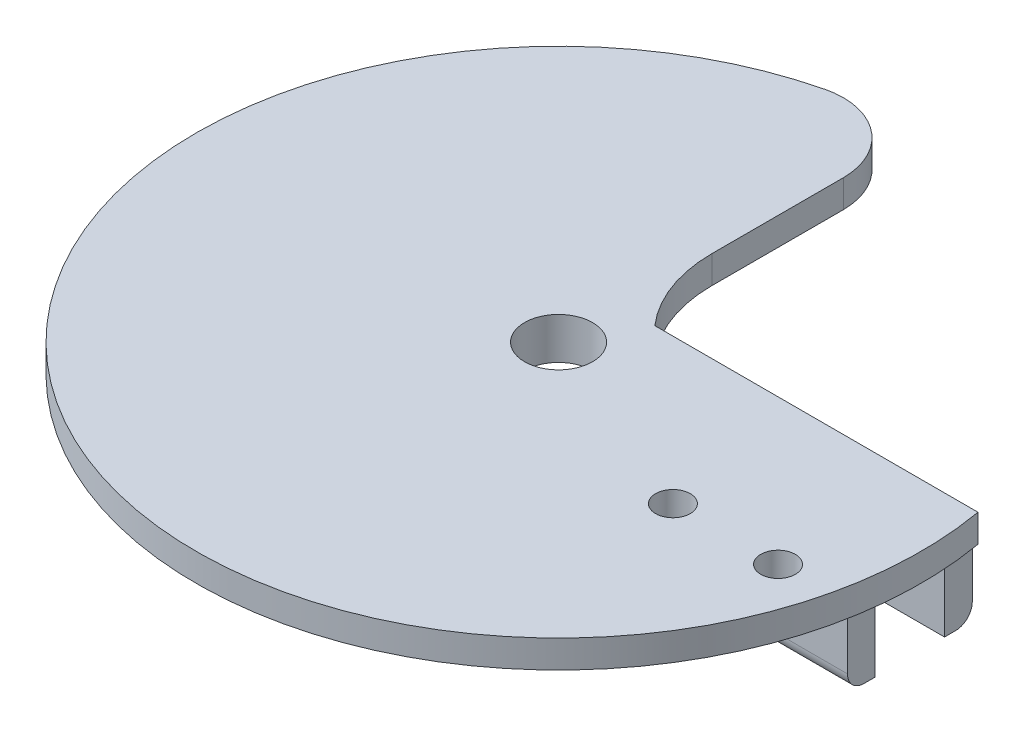
SolidWorks part; units mm, degrees
ref_plane "Front Plane" through (0, 0, 0) normal (0, 0, 1) x (1, 0, 0)
ref_plane "Top Plane" through (0, 0, 0) normal (0, 1, 0) x (1, 0, 0)
ref_plane "Right Plane" through (0, 0, 0) normal (1, 0, 0) x (0, 0, -1)
sketch "Sketch1" plane through (0, 0, 0) normal (0, 1, 0) x (1, 0, 0)
  line L0 (0, 0) -> (26.1327, 0) construction
  line L1 (0, 4.9) -> (0, 26.1327)
  line L2 (11.8897, 4.5) -> (1.9391, 4.5)
  line L3 (11.8897, 4.5) -> (25.3293, 4.5)
  line L4 (11.8897, 4.5) -> (11.8897, 2.5)
  line L5 (11.8897, 2.5) -> (25.3293, 2.5)
  line L6 (25.3293, 4.5) -> (25.3293, 2.5)
  line L7 (11.8897, -2.5) -> (25.3293, -2.5)
  line L8 (11.8897, -2.5) -> (11.8897, -4.5)
  line L9 (11.8897, -4.5) -> (25.3293, -4.5)
  line L10 (25.3293, -2.5) -> (25.3293, -4.5)
  line L11 (25.3293, 4.5) -> (25.7423, 4.5)
  circle A0 centre (0, 0) radius 2.45
  circle A1 centre (0, 0) radius 4.9
  arc A2 (0, 26.1327) -> (25.7423, 4.5) centre (0, 0) ccw
  circle A3 centre (14.2061, -5.9619) radius 1.25
  circle A4 centre (21.7863, -5.9619) radius 1.25
  point P21 (0, 0)
  point P22 (0, 0)
  point P23 (21.5088, -6.2022)
  point P24 (0, 0)
  point P25 (0, 0)
  point P26 (0, 0)
  point P27 (0, 0)
  point P28 (21.7863, -5.9619)
  dimension "D1" = 4.9
  dimension "D2" = 9.8
  dimension "D7" = 2.5
  dimension "D3" = 2
  dimension "D4" = 2
  dimension "D5" = 5
  dimension "D6" = 2.5
extrude "Boss-Extrude1" add sketch "Sketch1" against normal blind 2 contours L0 A1 L1 A2 L7 L10 L9 L8 | A1 L0 A2 L11 L6 L5 L4 L2 | L6 L3 L4 L5 | A1 | A0 | L9 L10 L7 L8 region at (13.6818, 0, -1.8351) region at (-4.3452, 0, 3.7979) region at (18.6095, 0, -3.5)
extrude "Boss-Extrude2" add sketch "Sketch1<3>" against normal blind 3 contours A0 A1 region at (0.9619, 0, -4.6632)
sketch "Sketch1<3>" plane through (0, 0, 0) normal (0, 1, 0) x (1, 0, 0) same geometry as "Sketch1"
extrude "Boss-Extrude3" add sketch "Sketch1<5>" against normal blind 7 contours L6 L3 L4 L5 | L10 L7 L8 L9 region at (18.6095, 0, -3.5) region at (18.6095, 0, 3.5)
sketch "Sketch1<5>" plane through (0, 0, 0) normal (0, 1, 0) x (1, 0, 0) same geometry as "Sketch1"
fillet "Fillet1" radius 10 1 edges at (0, -1, -4.9)
fillet "Fillet2" radius 5 1 edges at (0, -1, -26.1327)
fillet "Fillet3" radius 1.2 1 edges at (18.6095, -7, 4.5)
fillet "Fillet4" radius 1.2 1 edges at (18.6095, -7, -4.5)
equation "\"D2@Sketch1\"=\"D1@Sketch1\"*2"
equation "\"D4@Sketch1\"=\"D3@Sketch1\""
equation "\"D6@Sketch1\"=\"D5@Sketch1\"/2"
